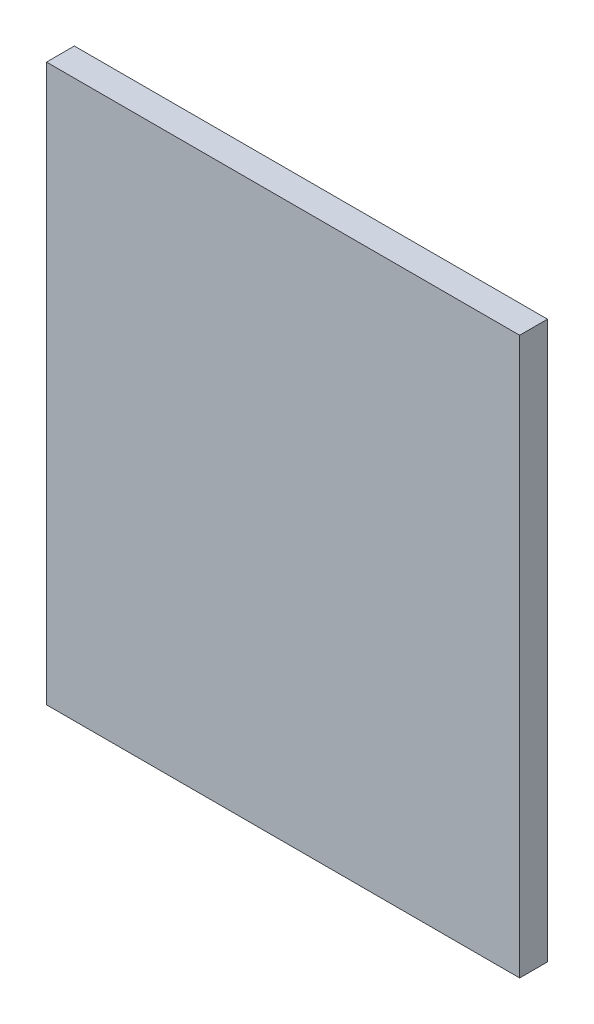
SolidWorks part; units mm, degrees
ref_plane "Front Plane" through (0, 0, 0) normal (0, 0, 1) x (1, 0, 0)
ref_plane "Top Plane" through (0, 0, 0) normal (0, 1, 0) x (1, 0, 0)
ref_plane "Right Plane" through (0, 0, 0) normal (1, 0, 0) x (0, 0, -1)
sketch "Sketch1" plane through (0, 0, 0) normal (0, 0, 1) x (1, 0, 0)
  line L1 (0, 0) -> (170, 0)
  line L2 (0, 0) -> (0, 200)
  line L3 (0, 200) -> (170, 200)
  line L4 (170, 0) -> (170, 200)
  dimension "D1" = 200
  dimension "D2" = 170
extrude "Bottom Outer Casing" add sketch "Sketch1" along normal blind 10
